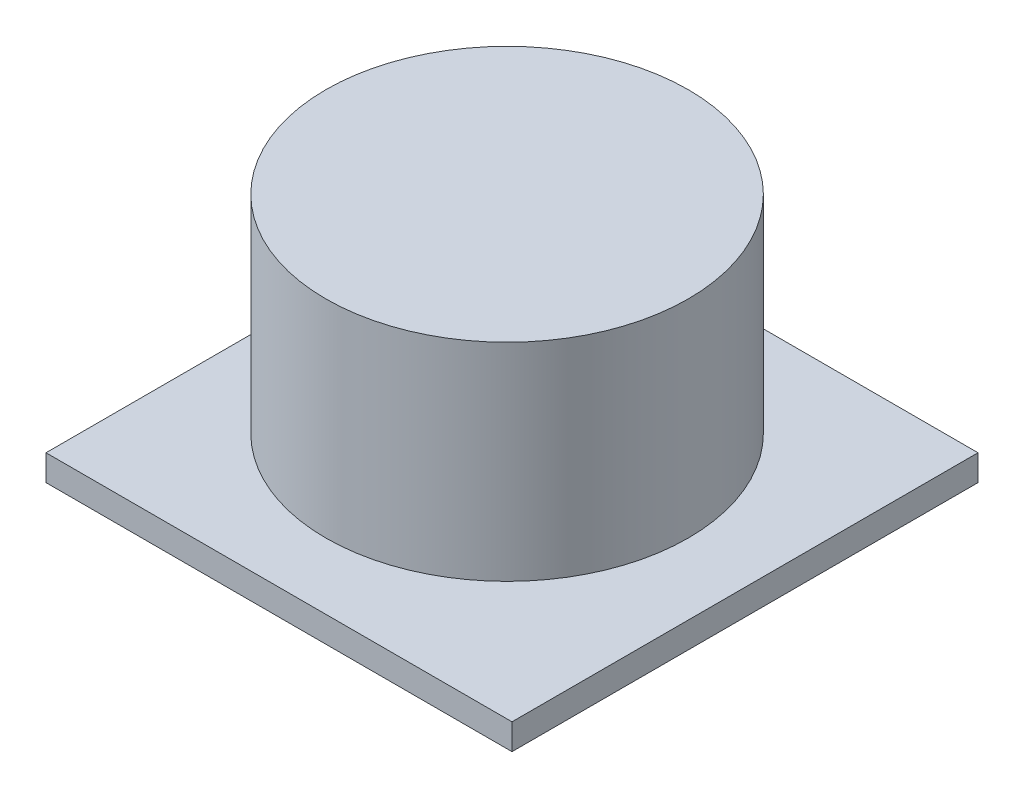
SolidWorks part; units mm, degrees
ref_plane "Front Plane" through (0, 0, 0) normal (0, 0, 1) x (1, 0, 0)
ref_plane "Top Plane" through (0, 0, 0) normal (0, 1, 0) x (1, 0, 0)
ref_plane "Right Plane" through (0, 0, 0) normal (1, 0, 0) x (0, 0, -1)
sketch "Sketch1" plane through (0, 0, 0) normal (0, 1, 0) x (1, 0, 0)
  line L1 (-139.5918, 84.4898) -> (40.4082, 84.4898)
  line L2 (-139.5918, 84.4898) -> (-139.5918, -95.5102)
  line L3 (-139.5918, -95.5102) -> (40.4082, -95.5102)
  line L4 (40.4082, 84.4898) -> (40.4082, -95.5102)
  dimension "D1" = 180
extrude "Boss-Extrude1" add sketch "Sketch1" along normal blind 10
sketch "Sketch2" plane through (0, 10, 0) normal (0, 1, 0) x (1, 0, 0)
  circle A0 centre (-57.0067, 0) radius 70
  dimension "D1" = 140
extrude "Boss-Extrude2" add sketch "Sketch2" along normal blind 80
sketch "Sketch3" plane through (0, 0, 0) normal (0, 0, 1) x (1, 0, 0)
  line L1 (-89.8939, 69.2885) -> (-9.8939, 69.2885)
  line L2 (-89.8939, 69.2885) -> (-89.8939, 29.2885)
  line L3 (-89.8939, 29.2885) -> (-9.8939, 29.2885)
  line L4 (-9.8939, 69.2885) -> (-9.8939, 29.2885)
  dimension "D1" = 40
  dimension "D2" = 80
